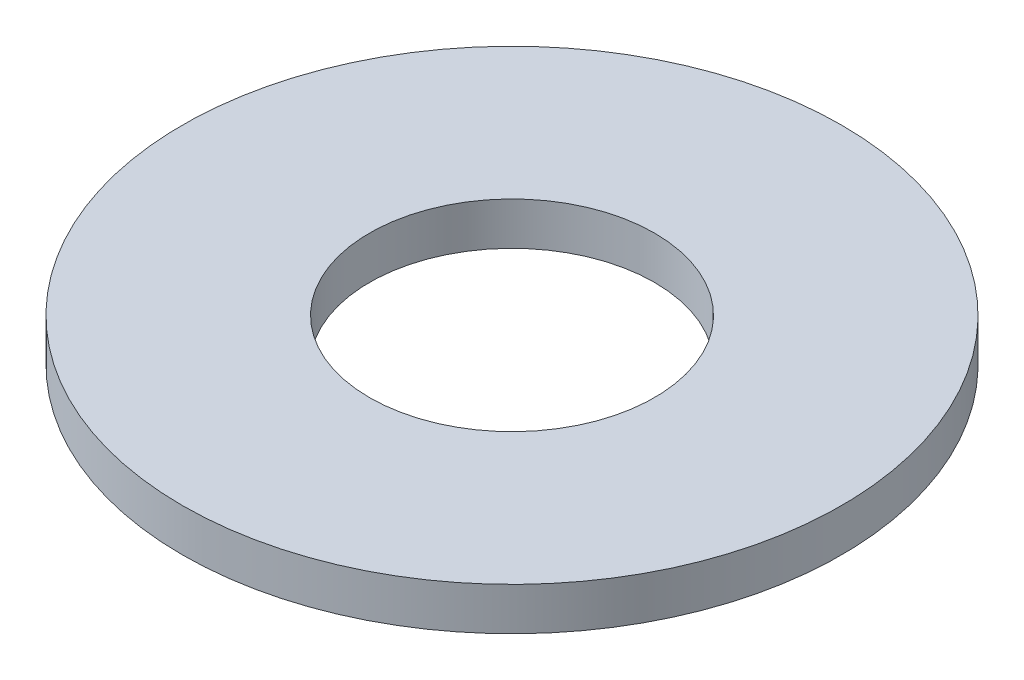
SolidWorks part; units mm, degrees
ref_plane "Front Plane" through (0, 0, 0) normal (0, 0, 1) x (1, 0, 0)
ref_plane "Top Plane" through (0, 0, 0) normal (0, 1, 0) x (1, 0, 0)
ref_plane "Right Plane" through (0, 0, 0) normal (1, 0, 0) x (0, 0, -1)
sketch "Sketch1" plane through (0, 0, 0) normal (0, 1, 0) x (1, 0, 0)
  circle A0 centre (0, 0) radius 92.5
  dimension "FLANGE_OD" = 185
extrude "Boss-Extrude1" add sketch "Sketch1" along normal blind 12
sketch "Sketch2" plane through (0, 0, 0) normal (0, 1, 0) x (1, 0, 0)
  circle A0 centre (0, 0) radius 40
  dimension "BORE_D" = 80
extrude "Cut-Extrude1" cut sketch "Sketch2" along normal through all
sketch "Sketch3" plane through (0, 12, 0) normal (0, 1, 0) x (1, 0, 0)
  circle A0 centre (0, 0) radius 30.0439 construction
  circle A1 centre (-30.0439, 0) radius 5.2892
  dimension "BOLT_D" = 10.5784
  dimension "BOLT_PCD" = 60.0877
extrude "Cut-Extrude2" cut sketch "Sketch3" against normal blind 11.3237 rebuild error yes
pattern_circular "CirPattern1" count 6 over 360 rebuild error yes
